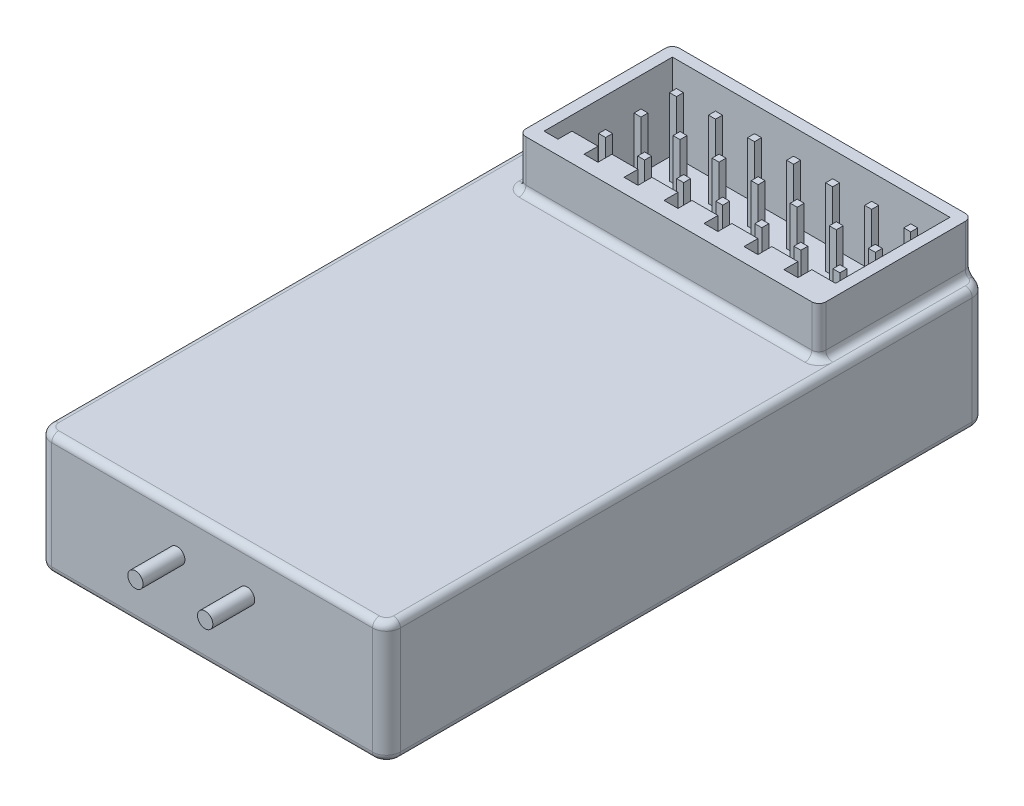
SolidWorks part; units mm, degrees
material "未指定"
ref_plane "正面" through (0, 0, 0) normal (0, 0, 1) x (1, 0, 0)
ref_plane "平面" through (0, 0, 0) normal (0, 1, 0) x (1, 0, 0)
ref_plane "右側面" through (0, 0, 0) normal (1, 0, 0) x (0, 0, -1)
sketch "ｽｹｯﾁ1" plane through (0, 0, 0) normal (0, 1, 0) x (1, 0, 0)
  line L1 (-12.5, 21.5) -> (12.5, 21.5)
  line L2 (-12.5, 21.5) -> (-12.5, -21.5)
  line L3 (-12.5, -21.5) -> (12.5, -21.5)
  line L4 (12.5, 21.5) -> (12.5, -21.5)
  line L5 (-12.5, 21.5) -> (12.5, -21.5) construction
  line L6 (-12.5, -21.5) -> (12.5, 21.5) construction
  point P0 (0, 0)
  dimension "D1" = 43
  dimension "D2" = 25
extrude "ﾎﾞｽ - 押し出し1" add sketch "ｽｹｯﾁ1" along normal mid plane 8.7
fillet "ﾌｨﾚｯﾄ1" radius 1 4 edges at (-12.5, 0, 21.5) (-12.5, 0, -21.5) (12.5, 0, -21.5) (12.5, 0, 21.5)
sketch "ｽｹｯﾁ2" plane through (0, 4.35, 0) normal (0, 1, 0) x (1, 0, 0)
  line L1 (11.5, 21.5) -> (-10, 21.5)
  line L2 (11.5, 21.5) -> (11.5, 10.5)
  line L3 (11.5, 10.5) -> (-10, 10.5)
  line L4 (-10, 21.5) -> (-10, 10.5)
  dimension "D1" = 21.5
  dimension "D2" = 11
extrude "ﾎﾞｽ - 押し出し2" add sketch "ｽｹｯﾁ2" along normal offset from surface (3.5 mm away) 12.2 up to face at (0, -4.35, 0)
fillet "ﾌｨﾚｯﾄ2" radius 0.5 23 edges at (12.2071, -4.35, 21.2071) (12.5, -4.35, 0) (12.2071, -4.35, -21.2071) (0, -4.35, -21.5) (-12.2071, -4.35, -21.2071) (-12.5, -4.35, 0) (-12.2071, -4.35, 21.2071) (0, -4.35, 21.5) (12.2071, 4.35, -21.2071) (12.5, 4.35, 0) (12.2071, 4.35, 21.2071) (0, 4.35, 21.5) (-12.2071, 4.35, 21.2071) (-12.5, 4.35, 0) (-12.2071, 4.35, -21.2071) (-10.75, 4.35, -21.5) (-10, 4.35, -16) (0.75, 4.35, -10.5) (11.5, 4.35, -16) (-10, 6.1, -10.5) (-10, 6.1, -21.5) (11.5, 6.1, -21.5) (11.5, 6.1, -10.5)
sketch "ｽｹｯﾁ3" plane through (0, 7.85, 0) normal (0, 1, 0) x (1, 0, 0)
  line L0 (-9.5, 10.5) -> (11, 10.5) construction
  line L1 (-9.2, 20.7) -> (10.7, 20.7)
  line L2 (-9.2, 20.7) -> (-9.2, 12.5)
  line L3 (-9.2, 12.5) -> (10.7, 12.5)
  line L4 (10.7, 20.7) -> (10.7, 12.5)
  line L5 (11, 21.5) -> (-9.5, 21.5) construction
  line L6 (11.5, 11) -> (11.5, 21) construction
  line L7 (-10, 21) -> (-10, 11) construction
  dimension "D1" = 2
  dimension "D2" = 0.8
  dimension "D3" = 0.8
  dimension "D4" = 0.8
extrude "ｶｯﾄ - 押し出し1" cut sketch "ｽｹｯﾁ3" against normal blind 6.1
sketch "ｽｹｯﾁ4" plane through (0, 7.85, 0) normal (0, 1, 0) x (1, 0, 0)
  line L0 (-6.3333, 12.5) -> (-5.3333, 12.5)
  line L1 (-9.2, 12.5) -> (-8.2, 12.5)
  line L2 (-9.2, 12.5) -> (-9.2, 11.5)
  line L3 (-9.2, 11.5) -> (-8.2, 11.5)
  line L4 (-8.2, 12.5) -> (-8.2, 11.5)
  line L5 (-6.3333, 12.5) -> (-6.3333, 11.5)
  line L6 (-6.3333, 11.5) -> (-5.3333, 11.5)
  line L7 (-5.3333, 12.5) -> (-5.3333, 11.5)
  line L8 (-3.4667, 12.5) -> (-2.4667, 12.5)
  line L9 (-3.4667, 12.5) -> (-3.4667, 11.5)
  line L10 (-3.4667, 11.5) -> (-2.4667, 11.5)
  line L11 (-2.4667, 12.5) -> (-2.4667, 11.5)
  line L12 (-0.6, 12.5) -> (0.4, 12.5)
  line L13 (-0.6, 12.5) -> (-0.6, 11.5)
  line L14 (-0.6, 11.5) -> (0.4, 11.5)
  line L15 (0.4, 12.5) -> (0.4, 11.5)
  line L16 (2.2667, 12.5) -> (3.2667, 12.5)
  line L17 (2.2667, 12.5) -> (2.2667, 11.5)
  line L18 (2.2667, 11.5) -> (3.2667, 11.5)
  line L19 (3.2667, 12.5) -> (3.2667, 11.5)
  line L20 (5.1333, 12.5) -> (6.1333, 12.5)
  line L21 (5.1333, 12.5) -> (5.1333, 11.5)
  line L22 (5.1333, 11.5) -> (6.1333, 11.5)
  line L23 (6.1333, 12.5) -> (6.1333, 11.5)
  line L24 (8, 12.5) -> (9, 12.5)
  line L25 (8, 12.5) -> (8, 11.5)
  line L26 (8, 11.5) -> (9, 11.5)
  line L27 (9, 12.5) -> (9, 11.5)
  line L28 (11.5, 11) -> (11.5, 21) construction
  line L29 (-9.2, 12.5) -> (10.7, 12.5) construction
  point P31 (9, 12.5)
  dimension "D1" = 1
  dimension "D3" = 2.5
  dimension "D2" = 7
extrude "ｶｯﾄ - 押し出し2" cut sketch "ｽｹｯﾁ4" against normal up to surface (6.1 mm away) up to face at (0.75, 1.75, -16.6)
sketch "ｽｹｯﾁ5" plane through (0, 1.75, 0) normal (0, 1, 0) x (1, 0, 0)
  line L0 (12.5, 20.5) -> (12.5, -20.5) construction
  line L1 (-8.8, 20.7) -> (10.7, 20.7) construction
  line L2 (-8.8, 20.7) -> (-8.8, 12.7) construction
  line L3 (-8.8, 12.7) -> (10.7, 12.7) construction
  line L4 (10.7, 20.7) -> (10.7, 12.7) construction
  line L7 (11, 21.5) -> (-9.5, 21.5) construction
  line L9 (-4.9, 19.49) -> (-4.4, 19.49)
  line L10 (-7.7, 19.49) -> (-7.2, 19.49)
  line L11 (-7.7, 19.49) -> (-7.7, 18.99)
  line L12 (-7.7, 18.99) -> (-7.2, 18.99)
  line L13 (-7.2, 19.49) -> (-7.2, 18.99)
  line L14 (-7.7, 19.49) -> (-7.2, 18.99) construction
  line L15 (-7.7, 18.99) -> (-7.2, 19.49) construction
  line L16 (-4.9, 19.49) -> (-4.9, 18.99)
  line L17 (-4.9, 18.99) -> (-4.4, 18.99)
  line L18 (-4.4, 19.49) -> (-4.4, 18.99)
  line L19 (-4.9, 19.49) -> (-4.4, 18.99) construction
  line L20 (-4.9, 18.99) -> (-4.4, 19.49) construction
  line L21 (-2.1, 19.49) -> (-1.6, 19.49)
  line L22 (-2.1, 19.49) -> (-2.1, 18.99)
  line L23 (-2.1, 18.99) -> (-1.6, 18.99)
  line L24 (-1.6, 19.49) -> (-1.6, 18.99)
  line L25 (-2.1, 19.49) -> (-1.6, 18.99) construction
  line L26 (-2.1, 18.99) -> (-1.6, 19.49) construction
  line L27 (0.7, 19.49) -> (1.2, 19.49)
  line L28 (0.7, 19.49) -> (0.7, 18.99)
  line L29 (0.7, 18.99) -> (1.2, 18.99)
  line L30 (1.2, 19.49) -> (1.2, 18.99)
  line L31 (0.7, 19.49) -> (1.2, 18.99) construction
  line L32 (0.7, 18.99) -> (1.2, 19.49) construction
  line L33 (3.5, 19.49) -> (4, 19.49)
  line L34 (3.5, 19.49) -> (3.5, 18.99)
  line L35 (3.5, 18.99) -> (4, 18.99)
  line L36 (4, 19.49) -> (4, 18.99)
  line L37 (3.5, 19.49) -> (4, 18.99) construction
  line L38 (3.5, 18.99) -> (4, 19.49) construction
  line L39 (6.3, 19.49) -> (6.8, 19.49)
  line L40 (6.3, 19.49) -> (6.3, 18.99)
  line L41 (6.3, 18.99) -> (6.8, 18.99)
  line L42 (6.8, 19.49) -> (6.8, 18.99)
  line L43 (6.3, 19.49) -> (6.8, 18.99) construction
  line L44 (6.3, 18.99) -> (6.8, 19.49) construction
  line L45 (9.1, 19.49) -> (9.6, 19.49)
  line L46 (9.1, 19.49) -> (9.1, 18.99)
  line L47 (9.1, 18.99) -> (9.6, 18.99)
  line L48 (9.6, 19.49) -> (9.6, 18.99)
  line L49 (9.1, 19.49) -> (9.6, 18.99) construction
  line L50 (9.1, 18.99) -> (9.6, 19.49) construction
  line L51 (-4.9, 16.95) -> (-4.4, 16.95)
  line L52 (-4.9, 16.95) -> (-4.9, 16.45)
  line L53 (-4.9, 16.45) -> (-4.4, 16.45)
  line L54 (-4.4, 16.95) -> (-4.4, 16.45)
  line L55 (-4.9, 16.95) -> (-4.4, 16.45) construction
  line L56 (-4.9, 16.45) -> (-4.4, 16.95) construction
  line L57 (-2.1, 16.95) -> (-1.6, 16.95)
  line L58 (-2.1, 16.95) -> (-2.1, 16.45)
  line L59 (-2.1, 16.45) -> (-1.6, 16.45)
  line L60 (-1.6, 16.95) -> (-1.6, 16.45)
  line L61 (-2.1, 16.95) -> (-1.6, 16.45) construction
  line L62 (-2.1, 16.45) -> (-1.6, 16.95) construction
  line L63 (0.7, 16.95) -> (1.2, 16.95)
  line L64 (0.7, 16.95) -> (0.7, 16.45)
  line L65 (0.7, 16.45) -> (1.2, 16.45)
  line L66 (1.2, 16.95) -> (1.2, 16.45)
  line L67 (0.7, 16.95) -> (1.2, 16.45) construction
  line L68 (0.7, 16.45) -> (1.2, 16.95) construction
  line L69 (3.5, 16.95) -> (4, 16.95)
  line L70 (3.5, 16.95) -> (3.5, 16.45)
  line L71 (3.5, 16.45) -> (4, 16.45)
  line L72 (4, 16.95) -> (4, 16.45)
  line L73 (3.5, 16.95) -> (4, 16.45) construction
  line L74 (3.5, 16.45) -> (4, 16.95) construction
  line L75 (6.3, 16.95) -> (6.8, 16.95)
  line L76 (6.3, 16.95) -> (6.3, 16.45)
  line L77 (6.3, 16.45) -> (6.8, 16.45)
  line L78 (6.8, 16.95) -> (6.8, 16.45)
  line L79 (6.3, 16.95) -> (6.8, 16.45) construction
  line L80 (6.3, 16.45) -> (6.8, 16.95) construction
  line L81 (9.1, 16.95) -> (9.6, 16.95)
  line L82 (9.1, 16.95) -> (9.1, 16.45)
  line L83 (9.1, 16.45) -> (9.6, 16.45)
  line L84 (9.6, 16.95) -> (9.6, 16.45)
  line L85 (9.1, 16.95) -> (9.6, 16.45) construction
  line L86 (9.1, 16.45) -> (9.6, 16.95) construction
  line L87 (-4.9, 14.41) -> (-4.4, 14.41)
  line L88 (-4.9, 14.41) -> (-4.9, 13.91)
  line L89 (-4.9, 13.91) -> (-4.4, 13.91)
  line L90 (-4.4, 14.41) -> (-4.4, 13.91)
  line L91 (-4.9, 14.41) -> (-4.4, 13.91) construction
  line L92 (-4.9, 13.91) -> (-4.4, 14.41) construction
  line L93 (-2.1, 14.41) -> (-1.6, 14.41)
  line L94 (-2.1, 14.41) -> (-2.1, 13.91)
  line L95 (-2.1, 13.91) -> (-1.6, 13.91)
  line L96 (-1.6, 14.41) -> (-1.6, 13.91)
  line L97 (-2.1, 14.41) -> (-1.6, 13.91) construction
  line L98 (-2.1, 13.91) -> (-1.6, 14.41) construction
  line L99 (0.7, 14.41) -> (1.2, 14.41)
  line L100 (0.7, 14.41) -> (0.7, 13.91)
  line L101 (0.7, 13.91) -> (1.2, 13.91)
  line L102 (1.2, 14.41) -> (1.2, 13.91)
  line L103 (0.7, 14.41) -> (1.2, 13.91) construction
  line L104 (0.7, 13.91) -> (1.2, 14.41) construction
  line L105 (3.5, 14.41) -> (4, 14.41)
  line L106 (3.5, 14.41) -> (3.5, 13.91)
  line L107 (3.5, 13.91) -> (4, 13.91)
  line L108 (4, 14.41) -> (4, 13.91)
  line L109 (3.5, 14.41) -> (4, 13.91) construction
  line L110 (3.5, 13.91) -> (4, 14.41) construction
  line L111 (6.3, 14.41) -> (6.8, 14.41)
  line L112 (6.3, 14.41) -> (6.3, 13.91)
  line L113 (6.3, 13.91) -> (6.8, 13.91)
  line L114 (6.8, 14.41) -> (6.8, 13.91)
  line L115 (6.3, 14.41) -> (6.8, 13.91) construction
  line L116 (6.3, 13.91) -> (6.8, 14.41) construction
  line L117 (9.1, 14.41) -> (9.6, 14.41)
  line L118 (9.1, 14.41) -> (9.1, 13.91)
  line L119 (9.1, 13.91) -> (9.6, 13.91)
  line L120 (9.6, 14.41) -> (9.6, 13.91)
  line L121 (9.1, 14.41) -> (9.6, 13.91) construction
  line L122 (9.1, 13.91) -> (9.6, 14.41) construction
  line L123 (-7.7, 16.95) -> (-7.2, 16.95)
  line L124 (-7.7, 16.95) -> (-7.7, 16.45)
  line L125 (-7.7, 16.45) -> (-7.2, 16.45)
  line L126 (-7.2, 16.95) -> (-7.2, 16.45)
  line L127 (-7.7, 16.95) -> (-7.2, 16.45) construction
  line L128 (-7.7, 16.45) -> (-7.2, 16.95) construction
  line L129 (-7.7, 14.41) -> (-7.2, 14.41)
  line L130 (-7.7, 14.41) -> (-7.7, 13.91)
  line L131 (-7.7, 13.91) -> (-7.2, 13.91)
  line L132 (-7.2, 14.41) -> (-7.2, 13.91)
  line L133 (-7.7, 14.41) -> (-7.2, 13.91) construction
  line L134 (-7.7, 13.91) -> (-7.2, 14.41) construction
  line L135 (10.7, 16.7) -> (-8.8, 16.7) construction
  point P9 (-7.45, 19.24)
  point P14 (-4.65, 19.24)
  point P20 (-1.85, 19.24)
  point P25 (0.95, 19.24)
  point P30 (3.75, 19.24)
  point P35 (6.55, 19.24)
  point P40 (9.35, 19.24)
  point P45 (-4.65, 16.7)
  point P50 (-1.85, 16.7)
  point P55 (0.95, 16.7)
  point P60 (3.75, 16.7)
  point P65 (6.55, 16.7)
  point P70 (9.35, 16.7)
  point P75 (-4.65, 14.16)
  point P80 (-1.85, 14.16)
  point P85 (0.95, 14.16)
  point P90 (3.75, 14.16)
  point P95 (6.55, 14.16)
  point P100 (9.35, 14.16)
  point P105 (-7.45, 16.7)
  point P110 (-7.45, 14.16)
  point P115 (1.6214, 17.0366)
  point P116 (0.95, 16.7)
  dimension "D1" = 1.8
  dimension "D2" = 8
  dimension "D3" = 0.8
  dimension "D4" = 19.5
  dimension "D5" = 0.5
  dimension "D8" = 17.3
  dimension "D9" = 2.54
  dimension "D6" = 7
  dimension "D7" = 3
extrude "ﾎﾞｽ - 押し出し3" add sketch "ｽｹｯﾁ5" along normal blind 5.5
sketch "ｽｹｯﾁ6" plane through (0, 0, 21.5) normal (0, 0, 1) x (1, 0, 0)
  line L0 (11, 4.35) -> (-9.5, 4.35) construction
  line L1 (0, 4.35) -> (0, -4.35) construction
  line L2 (11.5, -4.35) -> (-11.5, -4.35) construction
  circle A0 centre (-2.5, 1.35) radius 0.55
  circle A1 centre (2.5, 1.35) radius 0.55
  dimension "D1" = 1.1
  dimension "D2" = 3
  dimension "D3" = 5
extrude "ﾎﾞｽ - 押し出し4" add sketch "ｽｹｯﾁ6" along normal blind 3
